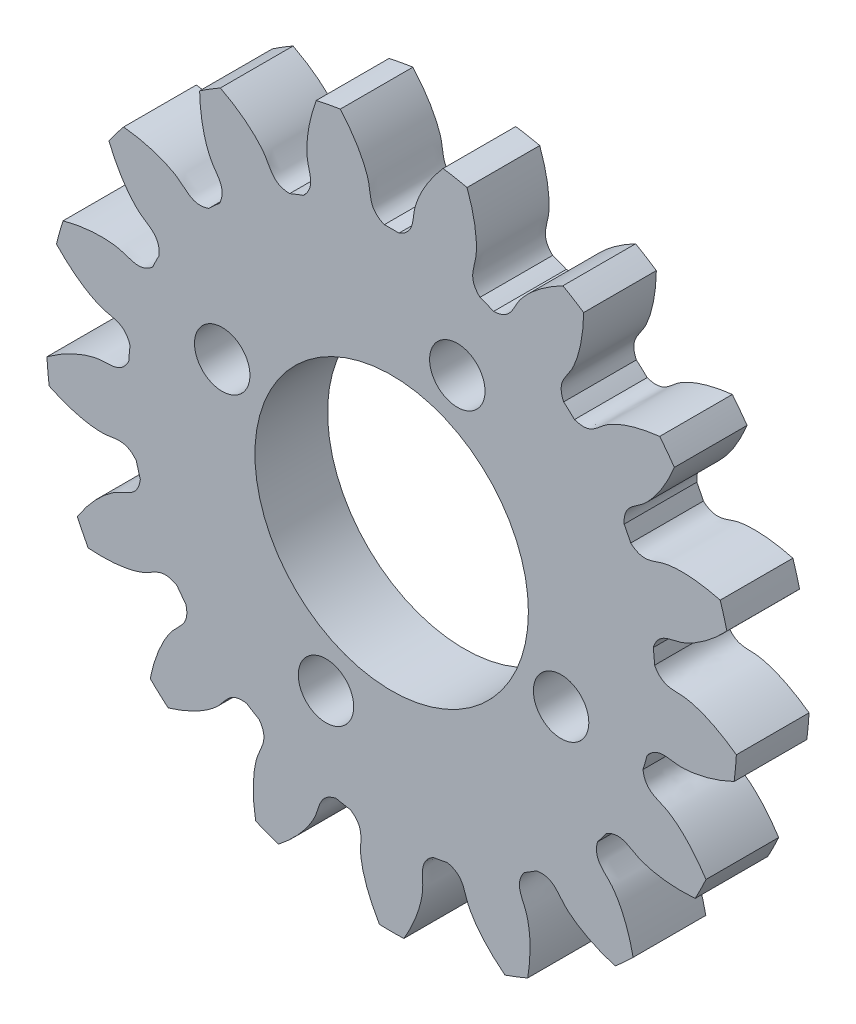
SolidWorks part; units mm, degrees
material "Thornel Mat VMA"
ref_plane "前视基准面" through (0, 0, 0) normal (0, 0, 1) x (1, 0, 0)
ref_plane "上视基准面" through (0, 0, 0) normal (0, 1, 0) x (1, 0, 0)
ref_plane "右视基准面" through (0, 0, 0) normal (1, 0, 0) x (0, 0, -1)
sketch "草图1" plane through (0, 0, 0) normal (0, 0, 1) x (1, 0, 0)
  circle A0 centre (0, 0) radius 19
extrude "凸台-拉伸1" add sketch "草图1" along normal blind 4
ref_axis "基准轴1" through (0, 0, 4) along (0, 0, -1)
sketch "草图2" plane through (0, 0, 0) normal (0, 0, 1) x (1, 0, 0)
  line L0 (0, 0) -> (0, 19) construction
  circle A0 centre (0, 0) radius 19 construction
  arc A1 (0.4034, 14.4944) -> (-0.4034, 14.4944) centre (0, 0) ccw
  arc A2 (6.2313, 21.4814) -> (-6.2313, 21.4814) centre (0, 0) ccw
  spline S0 degree 3 poles (0.4034, 14.4944) (1.2558, 14.8496) (1.1324, 15.5096) (1.2766, 16.1296) (1.29, 16.1823) (1.306, 16.2408) (1.3251, 16.3052) (1.3474, 16.3752) (1.3731, 16.4508) (1.4025, 16.5319) (1.4359, 16.6184) (1.4733, 16.7101) (1.5152, 16.8068) (1.5616, 16.9086) (1.6128, 17.0151) (1.669, 17.1264) (1.7304, 17.2421) (1.7972, 17.3621) (1.8696, 17.4863) (1.9478, 17.6145) (2.032, 17.7465) (2.1224, 17.8821) (2.2191, 18.0211) (2.3223, 18.1634) (2.4322, 18.3086) (2.5489, 18.4566) (2.6727, 18.6072) (2.8035, 18.7601) (2.9417, 18.9152) (3.0873, 19.0722) (3.2404, 19.2308) (3.4012, 19.3908) (3.5698, 19.552) (3.7462, 19.7141) (3.9307, 19.8769) (4.1233, 20.0401) (4.324, 20.2035) (4.533, 20.3667) (4.7503, 20.5295) (4.9761, 20.6917) (5.2103, 20.853) (5.453, 21.0131) (5.7916, 21.2269) (6.0532, 21.3811) (6.2313, 21.4814) knots 0 0 0 0 0.193883 0.199024 0.204851 0.211363 0.21856 0.226443 0.235011 0.244265 0.254205 0.264829 0.27614 0.288136 0.300817 0.314184 0.328236 0.342973 0.358397 0.374505 0.391299 0.408779 0.426944 0.445795 0.465331 0.485552 0.506459 0.528051 0.550329 0.573293 0.596941 0.621276 0.646296 0.672001 0.698392 0.725468 0.753229 0.781677 0.810809 0.840627 0.871131 0.90232 0.934195 1 1 1 1
  spline S1 degree 3 poles (-0.4034, 14.4944) (-1.2558, 14.8496) (-1.1324, 15.5096) (-1.2766, 16.1296) (-1.29, 16.1823) (-1.306, 16.2408) (-1.3251, 16.3052) (-1.3474, 16.3752) (-1.3731, 16.4508) (-1.4025, 16.5319) (-1.4359, 16.6184) (-1.4733, 16.7101) (-1.5152, 16.8068) (-1.5616, 16.9086) (-1.6128, 17.0151) (-1.669, 17.1264) (-1.7304, 17.2421) (-1.7972, 17.3621) (-1.8696, 17.4863) (-1.9478, 17.6145) (-2.032, 17.7465) (-2.1224, 17.8821) (-2.2191, 18.0211) (-2.3223, 18.1634) (-2.4322, 18.3086) (-2.5489, 18.4566) (-2.6727, 18.6072) (-2.8035, 18.7601) (-2.9417, 18.9152) (-3.0873, 19.0722) (-3.2404, 19.2308) (-3.4012, 19.3908) (-3.5698, 19.552) (-3.7462, 19.7141) (-3.9307, 19.8769) (-4.1233, 20.0401) (-4.324, 20.2035) (-4.533, 20.3667) (-4.7503, 20.5295) (-4.9761, 20.6917) (-5.2103, 20.853) (-5.453, 21.0131) (-5.7916, 21.2269) (-6.0532, 21.3811) (-6.2313, 21.4814) knots 0 0 0 0 0.193883 0.199024 0.204851 0.211363 0.21856 0.226443 0.235011 0.244265 0.254205 0.264829 0.27614 0.288136 0.300817 0.314184 0.328236 0.342973 0.358397 0.374505 0.391299 0.408779 0.426944 0.445795 0.465331 0.485552 0.506459 0.528051 0.550329 0.573293 0.596941 0.621276 0.646296 0.672001 0.698392 0.725468 0.753229 0.781677 0.810809 0.840627 0.871131 0.90232 0.934195 1 1 1 1
extrude "切除-拉伸1" cut sketch "草图2" along normal through all
pattern_circular "阵列(圆周)1" count 17 every 21.176 about axis through (0, 0, 4) along (0, 0, -1) of "切除-拉伸1"
sketch "草图3" plane through (0, 0, 0) normal (0, 0, 1) x (1, 0, 0)
  circle A0 centre (0, 0) radius 17 construction
  dimension "Dn" = 34
sketch "草图4" plane through (0, 0, 4) normal (0, 0, 1) x (1, 0, 0)
  circle A6 centre (0, 0) radius 7.525
  circle A7 centre (0, 0) radius 10 construction
  circle A8 centre (3.6124, 9.3247) radius 1.525
  circle A9 centre (9.3247, -3.6124) radius 1.525
  circle A10 centre (-3.6124, -9.3247) radius 1.525
  circle A11 centre (-9.3247, 3.6124) radius 1.525
  point P15 (0, 0)
  point P17 (0, 10)
  dimension "D1" = 15.05
  dimension "D2" = 20
  dimension "D3" = 3.05
  dimension "D4" = 21.176
extrude "切除-拉伸2" cut sketch "草图4" against normal blind 10
